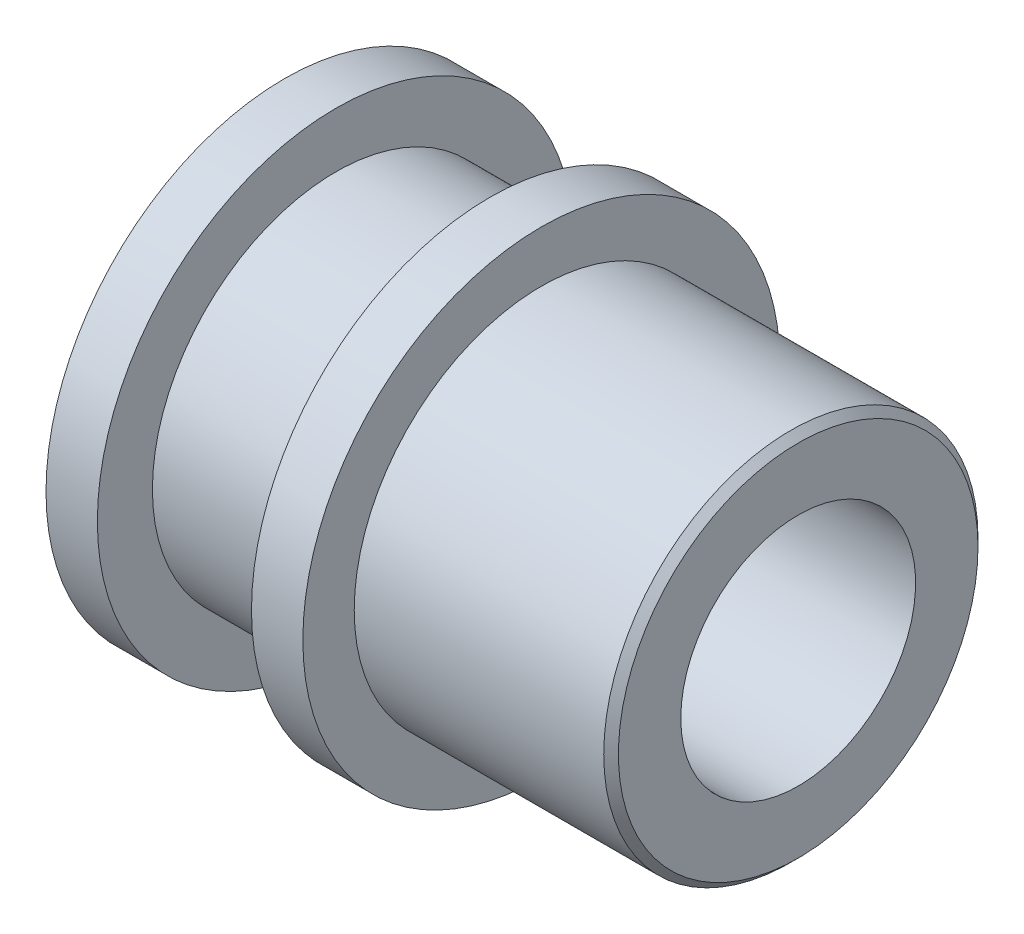
SolidWorks part; units mm, degrees
material "PTFE (general)"
ref_plane "Front Plane" through (0, 0, 0) normal (0, 0, 1) x (1, 0, 0)
ref_plane "Top Plane" through (0, 0, 0) normal (0, 1, 0) x (1, 0, 0)
ref_plane "Right Plane" through (0, 0, 0) normal (1, 0, 0) x (0, 0, -1)
sketch "Sketch1" plane through (0, 0, 0) normal (0, 1, 0) x (1, 0, 0)
  line L0 (0, 0) -> (70, 0)
  line L2 (0, 0) -> (0, -32.5)
  line L3 (0, -32.5) -> (7, -32.5)
  line L4 (7, -32.5) -> (7, -25)
  line L5 (7, -25) -> (28, -25)
  line L6 (28, -25) -> (28, -32.5)
  line L7 (28, -32.5) -> (35, -32.5)
  line L8 (35, -32.5) -> (35, -25.5)
  line L9 (35, -25.5) -> (70, -25.5)
  line L10 (70, -25.5) -> (70, 0)
revolve "Revolve1" add sketch "Sketch1" angle 360 about L0
sketch "Sketch2" plane through (0, 0, 0) normal (-1, 0, 0) x (0, 0, 1)
  circle A0 centre (0, 0) radius 26.5
extrude "Cut-Extrude1" cut sketch "Sketch2" against normal blind 2
chamfer "Chamfer1" distance 2 angle 45 1 edges at (2, 0, 26.5)
sketch "Sketch3" plane through (2, 0, 0) normal (-1, 0, 0) x (0, 0, 1)
  circle A0 centre (0, 0) radius 16
extrude "Cut-Extrude2" cut sketch "Sketch3" against normal through all
chamfer "Chamfer3" distance 1 angle 45 1 edges at (70, 0, 25.5)
